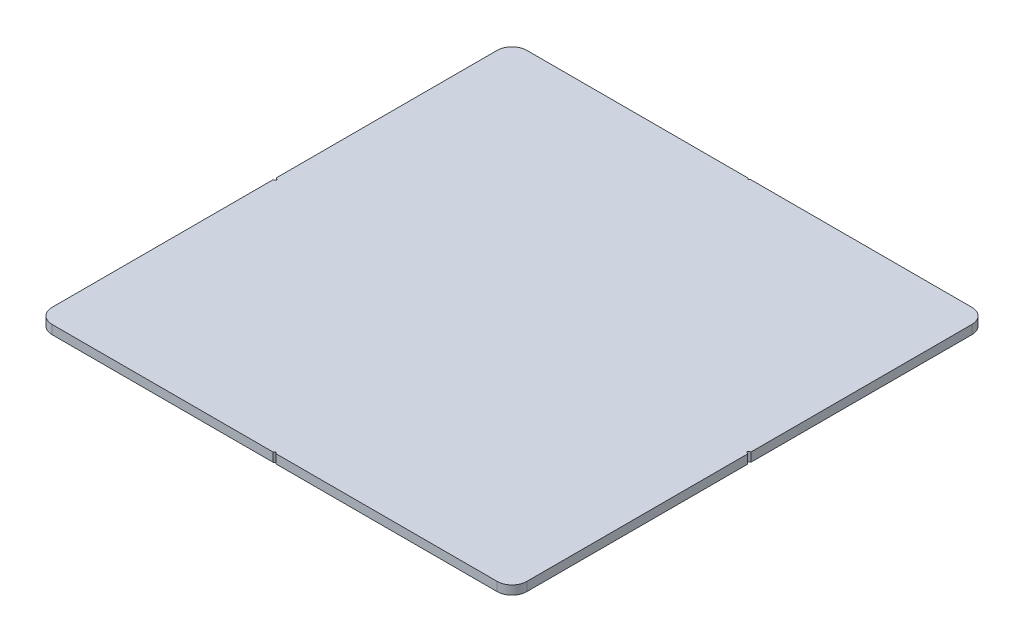
SolidWorks part; units mm, degrees
material "Клен"
ref_plane "Спереди" through (0, 0, 0) normal (0, 0, 1) x (1, 0, 0)
ref_plane "Сверху" through (0, 0, 0) normal (0, 1, 0) x (1, 0, 0)
ref_plane "Справа" through (0, 0, 0) normal (1, 0, 0) x (0, 0, -1)
sketch "Эскиз1" plane through (0, 0, 0) normal (0, 1, 0) x (1, 0, 0)
  line L0 (-199.4521, 0) -> (246.9406, 0) construction
  line L1 (-150, -160) -> (150, -160)
  line L2 (-160, -150) -> (-160, 150)
  line L3 (-150, 160) -> (150, 160)
  line L4 (160, -150) -> (160, 150)
  line L5 (-160, -160) -> (160, 160) construction
  line L6 (-160, 160) -> (160, -160) construction
  line L7 (0, -194.3379) -> (0, 187.7626) construction
  arc A0 (-150, -160) -> (-160, -150) centre (-150, -150) cw
  arc A1 (150, -160) -> (160, -150) centre (150, -150) ccw
  arc A2 (150, 160) -> (160, 150) centre (150, 150) cw
  arc A3 (-160, 150) -> (-150, 160) centre (-150, 150) cw
  point P0 (0, 0)
  point P10 (0, 0)
  dimension "D2" = 10
  dimension "D1" = 320
extrude "Бобышка-Вытянуть1" add sketch "Эскиз1" along normal blind 6
sketch "Эскиз2" plane through (0, 6, 0) normal (0, 1, 0) x (1, 0, 0)
  line L1 (0, -176.9605) -> (0, 172.8451) construction
  line L8 (0, 0) -> (-184.1552, 0) construction
  line L9 (-158.3663, 0) -> (-160, 1.2692)
  line L10 (-160, 150) -> (-160, -150) construction
  line L11 (-160, 1.2692) -> (-160, -1.2752)
  line L12 (-160, -1.2752) -> (-158.3663, 0)
  line L13 (160, -1.2752) -> (158.3663, 0)
  line L14 (160, 1.2692) -> (160, -1.2752)
  line L15 (158.3663, 0) -> (160, 1.2692)
  line L16 (0, 159.0596) -> (0.9404, 160)
  line L17 (150, 160) -> (-150, 160) construction
  line L18 (0.9404, 160) -> (-0.9404, 160)
  line L19 (-0.9404, 160) -> (0, 159.0596)
  line L20 (-0.9404, -160) -> (0, -159.0596)
  line L21 (0.9404, -160) -> (-0.9404, -160)
  line L22 (0, -159.0596) -> (0.9404, -160)
extrude "Вырез-Вытянуть1" cut sketch "Эскиз2" against normal through all
ref_plane "Плоскость1" through (0, 0, 0) normal (1, 0, 0) x (0, 0, -1)
